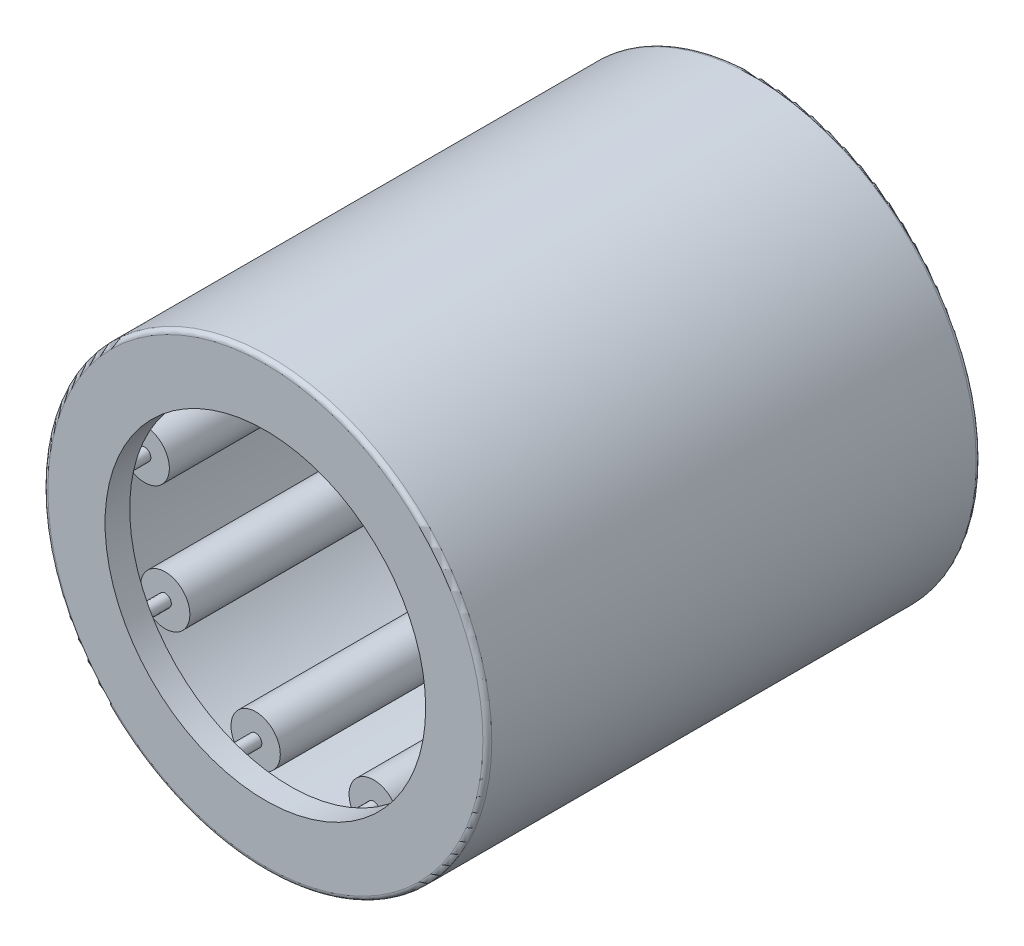
SolidWorks part; units mm, degrees
ref_plane "Front Plane" through (0, 0, 0) normal (0, 0, 1) x (1, 0, 0)
ref_plane "Top Plane" through (0, 0, 0) normal (0, 1, 0) x (1, 0, 0)
ref_plane "Right Plane" through (0, 0, 0) normal (1, 0, 0) x (0, 0, -1)
sketch "Sketch1" plane through (0, 0, 0) normal (1, 0, 0) x (0, 0, -1)
  line L0 (-7.9375, 0) -> (7.9375, 0) construction
  line L1 (0, 0) -> (0, 7.1438) construction
  line L2 (-7.9375, 0) -> (-7.9375, 7.1437) construction
  line L3 (-7.9375, 7.1437) -> (7.9375, 7.1437)
  line L4 (7.9375, 7.1437) -> (7.9375, 0) construction
  line L5 (7.9375, 0) -> (7.1438, 0) construction
  line L6 (7.1438, 0) -> (7.1438, 6.35) construction
  line L7 (7.1438, 6.35) -> (-7.1438, 6.35)
  line L8 (-7.1438, 6.35) -> (-7.1438, 0) construction
  line L9 (-7.1438, 0) -> (-7.9375, 0) construction
  line L10 (-7.9375, 7.1437) -> (-7.9375, 5.1594)
  line L11 (-7.9375, 5.1594) -> (-7.1438, 5.1594)
  line L12 (-7.1438, 5.1594) -> (-7.1438, 6.35)
  line L13 (7.1438, 7.1438) -> (7.1438, 6.35) construction
  line L14 (7.1438, 6.35) -> (7.1438, 5.1594)
  line L15 (7.1438, 5.1594) -> (7.9375, 5.1594)
  line L16 (7.9375, 5.1594) -> (7.9375, 7.1437)
  line L17 (7.1438, 6.35) -> (7.1438, 5.5563) construction
  line L18 (7.1438, 5.5563) -> (7.1438, 4.7625) construction
  point P5 (0, 4.7625)
  dimension "Width" = 15.875
  dimension "OD" = 14.2875
  dimension "Shaft Dia" = 9.525
revolve "Revolve1" add sketch "Sketch1" angle 360 about L0
sketch "Sketch2" plane through (0, 0, 0) normal (1, 0, 0) x (0, 0, -1)
  line L0 (7.1438, 6.35) -> (-7.1438, 6.35) construction
  line L1 (-6.35, 5.5563) -> (6.35, 5.5563) construction
  line L2 (-6.35, 5.5563) -> (-6.35, 6.35) construction
  line L3 (-6.35, 6.35) -> (6.35, 6.35)
  line L4 (6.35, 5.5563) -> (6.35, 6.35) construction
  line L5 (7.1438, 5.1594) -> (7.9375, 5.1594) construction
  line L6 (-7.1438, 5.5562) -> (-6.35, 5.5563) construction
  line L7 (6.35, 5.5563) -> (7.1438, 5.5562) construction
  line L8 (-7.9375, 5.1594) -> (-7.1438, 5.1594) construction
  line L9 (-6.35, 5.7547) -> (-6.35, 5.3578) construction
  line L10 (-7.1438, 5.5562) -> (-7.1438, 5.1594) construction
  line L11 (-6.35, 6.35) -> (-6.35, 5.7547)
  line L12 (6.35, 6.35) -> (6.35, 5.7547)
  line L13 (6.35, 5.7547) -> (-6.35, 5.7547)
  line L14 (0, 6.35) -> (0, 4.7625) construction
  line L15 (-7.1438, 5.1594) -> (-7.1438, 6.35) construction
  line L16 (-6.35, 5.3578) -> (-7.1438, 5.3578) construction
  line L17 (0, 0) -> (7.9375, 0) construction
  line L31 (7.9375, -7.1438) -> (7.9375, 7.1437) construction
  point P16 (0, 5.5563)
revolve "Revolve2" add sketch "Sketch2" angle 360 about L1
sketch "Sketch3" plane through (0, 0, 0) normal (1, 0, 0) x (0, 0, -1)
  line L0 (7.1438, 6.35) -> (7.1438, 5.1594) construction
  line L1 (-7.1438, 5.5562) -> (7.1438, 5.5562)
  line L2 (-7.1438, 5.5562) -> (-7.1438, 5.7547)
  line L3 (-7.1438, 5.7547) -> (7.1438, 5.7547)
  line L4 (7.1438, 5.5562) -> (7.1438, 5.7547)
  line L5 (0, 0) -> (7.9375, 0) construction
  line L6 (7.9375, -7.1438) -> (7.9375, 7.1437) construction
revolve "Revolve3" add sketch "Sketch3" angle 360 about L1
ref_axis "Axis1" through (0, 0, -7.9375) along (0, 0, 1)
pattern_circular "CirPattern1" count 9 every 40 about axis through (0, 0, -7.9375) along (0, 0, 1) of bodies 166 167
fillet "Fillet1" radius 0.1429 2 edges at (7.1438, 0, -7.9375) (7.1438, 0, 7.9375)
sketch "Sketch4" plane through (0, 0, 0) normal (1, 0, 0) x (0, 0, -1)
  line L1 (7.7946, 4.7625) -> (6.35, 4.7625)
  line L2 (7.7946, 4.7625) -> (7.7946, 5.1594)
  line L3 (7.7946, 5.1594) -> (6.35, 5.1594)
  line L4 (6.35, 4.7625) -> (6.35, 5.1594)
  line L5 (-7.9375, 5.1594) -> (-7.1438, 5.1594) construction
  line L6 (7.7946, -7.1438) -> (7.7946, 7.1437) construction
  line L7 (6.35, 6.35) -> (6.35, 5.7547) construction
revolve "Revolve4" [suppressed] add sketch "Sketch4" angle 360 about L0
sketch "Sketch5" plane through (0, 0, 0) normal (1, 0, 0) x (0, 0, -1)
  line L0 (-7.7946, 7.1437) -> (-7.7946, -7.1438) construction
  line L1 (-6.35, 4.7625) -> (-7.7946, 4.7625)
  line L2 (-6.35, 4.7625) -> (-6.35, 5.1594)
  line L3 (-6.35, 5.1594) -> (-7.7946, 5.1594)
  line L4 (-7.7946, 4.7625) -> (-7.7946, 5.1594)
  line L6 (-6.35, 6.35) -> (-6.35, 5.7547) construction
  line L7 (-7.9375, 5.1594) -> (-7.1438, 5.1594) construction
revolve "Revolve5" [suppressed] add sketch "Sketch5" angle 360 about L0
sketch "Front View" plane through (0, 0, 0) normal (0, 0, 1) x (1, 0, 0)
  circle A0 centre (0, 0) radius 4.7625 construction
  circle A1 centre (0, 0) radius 7.1438 construction
  dimension "OD" = 14.2875
  dimension "ID" = 9.525
sketch "Right View" plane through (0, 0, 0) normal (1, 0, 0) x (0, 0, -1)
  line L0 (-7.9375, 7.1438) -> (7.9375, 7.1438) construction
  dimension "Width" = 15.875
ref_axis "Center Axis 1" through (0, 0, -7.7946) along (0, 0, 1)
ref_plane "Contact Plane 1" through (0, 0, 7.9375) normal (0, 0, 1) x (1, 0, 0)
ref_plane "Contact Plane 2" through (0, 0, -7.9375) normal (0, 0, -1) x (-1, 0, 0)
ref_axis "Axis2" through (0, 0, -17.9321) along (0, 0, 1)
equation "\"Rollers@CirPattern1\" = \"OD@Sketch1\"*16"
equation "\"D1@Fillet1\" = \"OD@Sketch1\"*.01"
equation "\"Angle@CirPattern1\"= 360 / \"Rollers@CirPattern1\""
equation "\"OD@Front View\"=\"OD@Sketch1\""
equation "\"ID@Front View\"=\"Shaft Dia@Sketch1\""
equation "\"Width@Right View\"=\"Width@Sketch1\""
